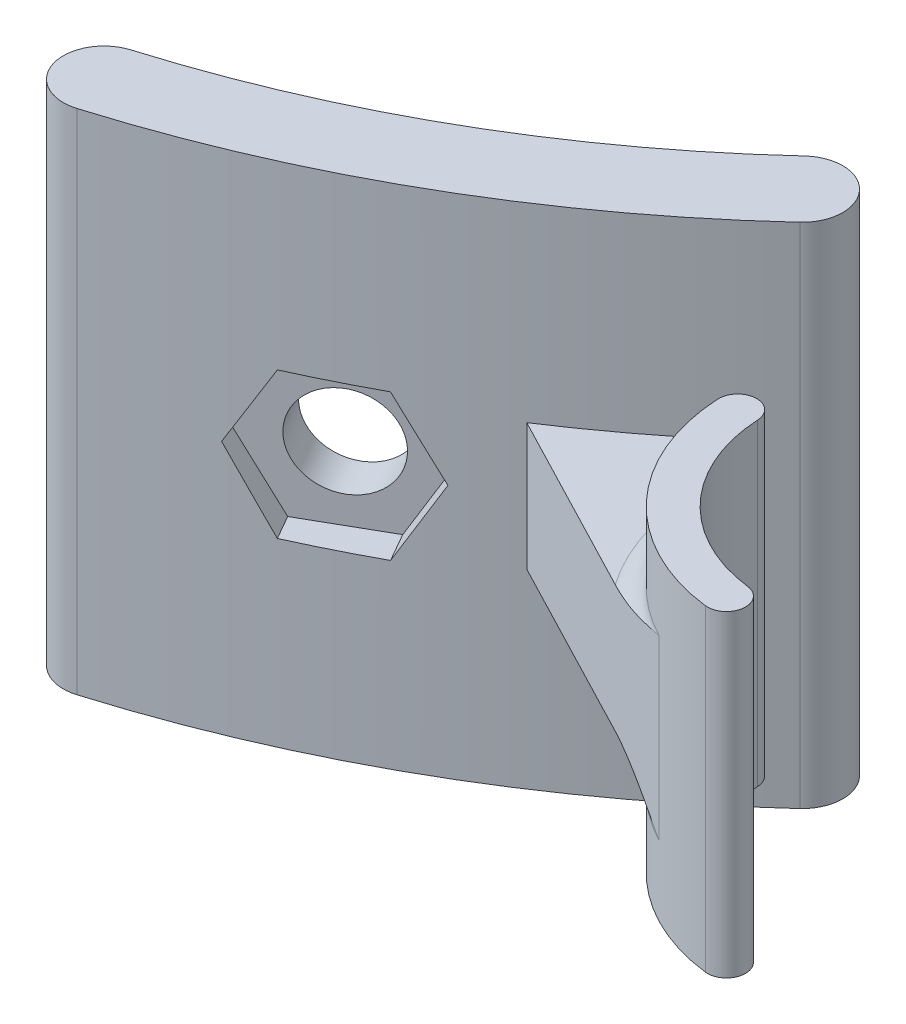
SolidWorks part; units mm, degrees
note: The reader was unsure of these and kept them because the rebuilt part matched: shared geometry of "Sketch2<4>", "Sketch5<3>".
ref_plane "Front Plane" through (0, 0, 0) normal (0, 0, 1) x (1, 0, 0)
ref_plane "Top Plane" through (0, 0, 0) normal (0, 1, 0) x (1, 0, 0)
ref_plane "Right Plane" through (0, 0, 0) normal (1, 0, 0) x (0, 0, -1)
sketch "Sketch1" plane through (0, 0, 0) normal (0, 1, 0) x (1, 0, 0)
  arc A0 (0, 0) -> (-17.5, -10) centre (-30.5092, 33.0785) cw construction
  arc A1 (-17.0375, -11.5317) -> (1.0848, -1.1761) centre (-30.5092, 33.0785) ccw
  arc A2 (-17.9625, -8.4683) -> (-1.0848, 1.1761) centre (-30.5092, 33.0785) ccw
  arc A3 (-17.9625, -8.4683) -> (-17.0375, -11.5317) centre (-17.5, -10) ccw
  arc A4 (1.0848, -1.1761) -> (-1.0848, 1.1761) centre (0, 0) ccw
  point P3 (-8.1829, -5.9924)
  dimension "D1" = 3.2
  dimension "D2" = 45
  dimension "D3" = 10
  dimension "D4" = 17.5
extrude "Boss-Extrude1" add sketch "Sketch1" along normal mid plane 20 contours A2 A4 A1 A3
sketch "Sketch2" plane through (0, 0, 0) normal (0, 1, 0) x (1, 0, 0)
  line L0 (-1.3154, -3.2434) -> (1.8153, -5.7458)
  line L1 (-4.9549, -5.8899) -> (5.9125, -11.5458)
  arc A0 (2.5, -5.0379) -> (8.639, -11.6191) centre (9.4904, -4.6711) ccw construction
  arc A1 (1.751, -5.0772) -> (8.5478, -12.3636) centre (9.4904, -4.6711) ccw
  arc A2 (3.249, -4.9986) -> (8.7302, -10.8747) centre (9.4904, -4.6711) ccw
  arc A3 (3.249, -4.9986) -> (1.751, -5.0772) centre (2.5, -5.0379) ccw
  arc A4 (8.5478, -12.3636) -> (8.7302, -10.8747) centre (8.639, -11.6191) ccw
  arc A5 (-17.0375, -11.5317) -> (1.0848, -1.1761) centre (-30.5092, 33.0785) ccw construction
  arc A6 (-4.9549, -5.8899) -> (-1.3154, -3.2434) centre (-30.5092, 33.0785) ccw
  arc A7 (0, 0) -> (-17.5, -10) centre (-30.5092, 33.0785) cw construction
  arc A8 (-17.9625, -8.4683) -> (-1.0848, 1.1761) centre (-30.5092, 33.0785) ccw construction
  arc A9 (22.6933, 19.1323) -> (-23.757, -21.5054) centre (-30.5092, 33.0785) cw construction
  point P3 (4.3717, -9.4459)
  dimension "D1" = 1.5
  dimension "D2" = 4.5
  dimension "D4" = 3.5
  dimension "D9" = 10
  dimension "D10" = 2.5
  dimension "D5" = 7
  dimension "D3" = 5.8
  dimension "D6" = 9
extrude "Boss-Extrude2" add sketch "Sketch2" along normal mid plane 5 separate body
extrude "Boss-Extrude3" add sketch "Sketch2<4>" along normal mid plane 12.5 contours A1 A4 A2 A3
sketch "Sketch2<4>" plane through (0, 0, 0) normal (0, 1, 0) x (1, 0, 0) same geometry as "Sketch2"
ref_plane "Plane1" through (-0.7737, 0, -1.3539) normal (-0.4961, 0, -0.8682) x (-0.8682, 0, 0.4961)
sketch "Sketch5" plane through (-0.7737, 0, -1.3539) normal (-0.4961, 0, -0.8682) x (-0.8682, 0, 0.4961)
  line L0 (0.3583, 0) -> (19.7973, 0) construction
  line L4 (0.3583, -10) -> (19.7973, -10)
  line L5 (19.7973, -10) -> (19.7973, 10)
  line L6 (19.7973, 10) -> (0.3583, 10)
  line L7 (0.3583, 10) -> (0.3583, -10)
  line L8 (0.3583, -10) -> (19.7973, -10)
  line L9 (19.7973, -10) -> (19.7973, 10)
  line L10 (19.7973, 10) -> (0.3583, 10)
  line L11 (0.3583, 10) -> (0.3583, -10)
  line L13 (14.4572, -2.875) -> (16.1171, 0)
  line L14 (16.1171, 0) -> (14.4572, 2.875)
  line L15 (14.4572, 2.875) -> (11.1374, 2.875)
  line L16 (11.1374, 2.875) -> (9.4776, 0)
  line L17 (9.4776, 0) -> (11.1374, -2.875)
  line L18 (11.1374, -2.875) -> (14.4572, -2.875)
  circle A0 centre (12.7973, 0) radius 2.875 construction
  point P5 (0.3583, 10)
  point P6 (12.7973, 0)
  dimension "D2" = 7
  dimension "D3" = 5.75
  dimension "D1" = 0
hole_wizard "CSK for M3 Flat Head Machine Screw1" positions "Sketch5" profile "Sketch6" countersink size "M3" standard "ANSI Metric"
sketch "Sketch6" plane through (-11.8848, 0, 4.9953) normal (0, 1, 0) x (-0.8682, 0, 0.4961)
  line L0 (0, 0) -> (0, 16.957)
  line L1 (0, 16.957) -> (1.8, 16.957)
  line L2 (1.8, 16.957) -> (1.8, 1.35)
  line L3 (1.8, 1.35) -> (3.15, 0)
  line L5 (3.15, 0) -> (0, 0)
  line L6 (-1.8, 1.35) -> (-3.15, 0) construction
  line L11 (0, -6.35) -> (0, 107.95) construction
  dimension "Thru Hole Dia." = 3.6
  dimension "Thru Hole Depth" = 16.957
  dimension "Near C'Sink Dia." = 6.3
  dimension "Near C'Sink Angle" = 90
fillet "Fillet1" radius 1 2 edges at (3.1605, -2.5, 9.1427) (3.1605, 2.5, 9.1427)
extrude "Cut-Extrude1" cut sketch "Sketch5<3>" against normal blind 2 from offset 3 contours L17 L18 L13 L14 L15 L16
sketch "Sketch5<3>" plane through (-0.7737, 0, -1.3539) normal (-0.4961, 0, -0.8682) x (-0.8682, 0, 0.4961) same geometry as "Sketch5"
